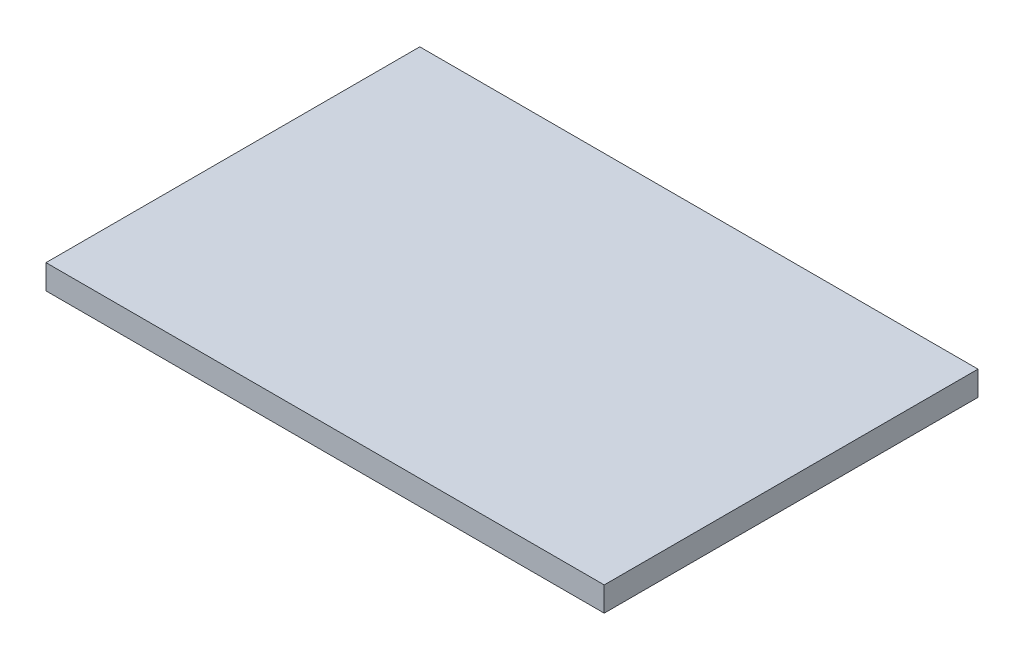
SolidWorks part; units mm, degrees
material "ABS"
ref_plane "Front Plane" through (0, 0, 0) normal (0, 0, 1) x (1, 0, 0)
ref_plane "Top Plane" through (0, 0, 0) normal (0, 1, 0) x (1, 0, 0)
ref_plane "Right Plane" through (0, 0, 0) normal (1, 0, 0) x (0, 0, -1)
sketch "Sketch1" plane through (0, 0, 0) normal (0, 1, 0) x (1, 0, 0)
  line L1 (-34.2, -22.9) -> (34.2, -22.9)
  line L2 (-34.2, -22.9) -> (-34.2, 22.9)
  line L3 (-34.2, 22.9) -> (34.2, 22.9)
  line L4 (34.2, -22.9) -> (34.2, 22.9)
  line L5 (-34.2, -22.9) -> (34.2, 22.9) construction
  line L6 (-34.2, 22.9) -> (34.2, -22.9) construction
  point P0 (0, 0)
  dimension "D1" = 45.8
  dimension "D2" = 68.4
extrude "Boss-Extrude1" add sketch "Sketch1" along normal blind 3
equation "\"smallPulleyTeeth\"= 30"
equation "\"largePulleyTeeth\"= 30"
equation "\"eighthThick\"= 3.0mm"
equation "\"sixteenthThick\" = 1.7mm"
equation "\"quarterThick\"=6.0mm"
equation "\"OD\" = 145mm"
equation "\"puckAngle\" = 60.5deg"
equation "\"puckDiam\" = 76.5mm"
equation "\"puckDist\" = 85mm"
equation "\"scoopFillet\" = 5mm"
equation "\"axlePress\" = 5.9mm"
equation "\"press\" = 0.2mm"
equation "\"wheelClear\" = 0.3mm"
equation "\"10-32clear\" = 4.8mm"
equation "\"10-32tap\" = 4.45mm"
equation "\"6-32clear\" = 3.3mm"
equation "\"8-32clear\" = 4.0mm"
equation "\"4-40clear\" = 3.0mm"
equation "\"wheelHeight\" = 22mm"
equation "\"wheelWell\" = 65mm"
equation "\"ledSmall\" = 3.1mm"
equation "\"ledLarge\" = 4.2mm"
equation "\"ledLength\" = 4.2mm"
equation "\"4-40close\" = 2.7mm"
equation "\"4-40nutThick\" = 2.2mm"
equation "\"4-40nutWidth\" = 6.2mm"
equation "\"4-40insertHeight\" = 3.5mm"
equation "\"4-40insert\" = 4mm"
equation "\"D1@Boss-Extrude1\"=\"eighthThick\""
